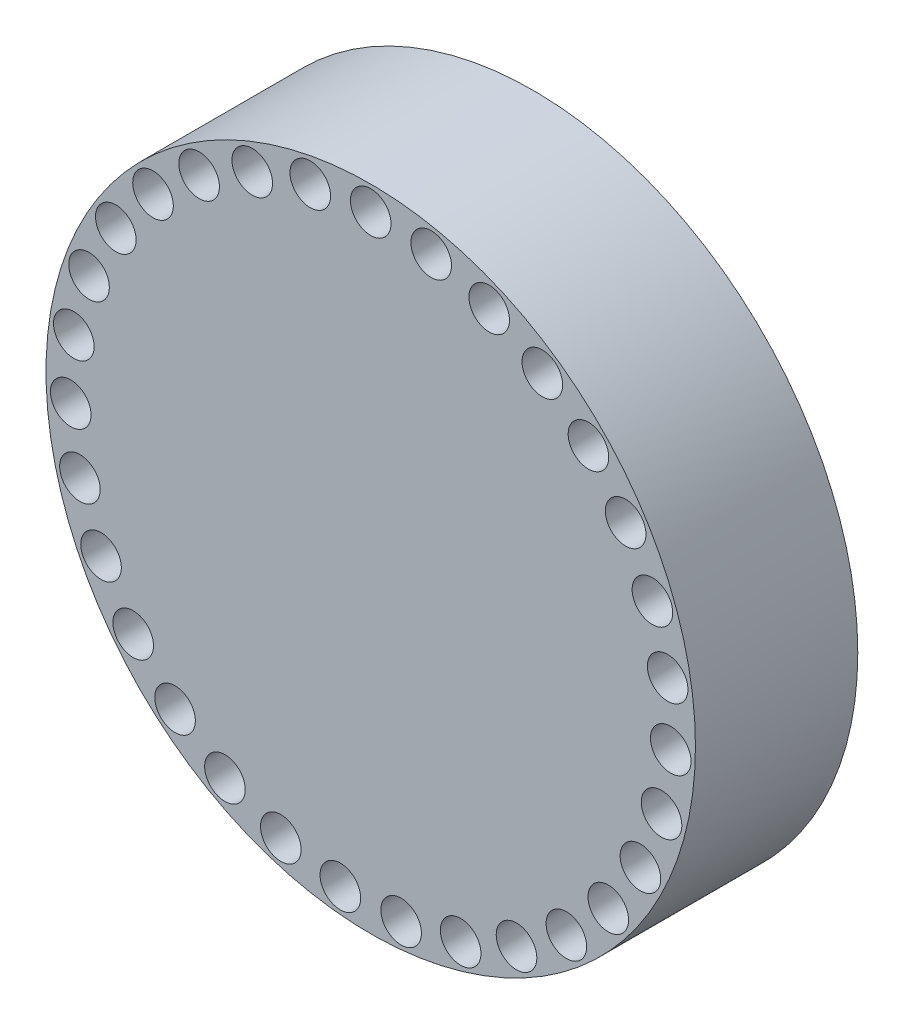
SolidWorks part; units mm, degrees
ref_plane "Front Plane" through (0, 0, 0) normal (0, 0, 1) x (1, 0, 0)
ref_plane "Top Plane" through (0, 0, 0) normal (0, 1, 0) x (1, 0, 0)
ref_plane "Right Plane" through (0, 0, 0) normal (1, 0, 0) x (0, 0, -1)
sketch "Sketch1" plane through (0, 0, 0) normal (0, 0, 1) x (1, 0, 0)
  circle A1 centre (0, 0) radius 46.9945 construction
  circle A2 centre (0, 0) radius 50.8
  dimension "D1" = 93.9889
  dimension "D2" = 101.6
extrude "Boss-Extrude1" add sketch "Sketch1" along normal blind 25.4
sketch "Sketch2" plane through (0, 0, 25.4) normal (0, 0, 1) x (1, 0, 0)
  circle A0 centre (0, 46.9945) radius 3.175
  circle A1 centre (0, 0) radius 46.9945 construction
  point P4 (0, 0)
  dimension "D1" = 6.35
extrude "Cut-Extrude1" cut sketch "Sketch2" against normal through all
pattern_circular "CirPattern1" count 31 over 360 about axis through (0, 0, 25.4) along (0, 0, -1) of "Cut-Extrude1"
